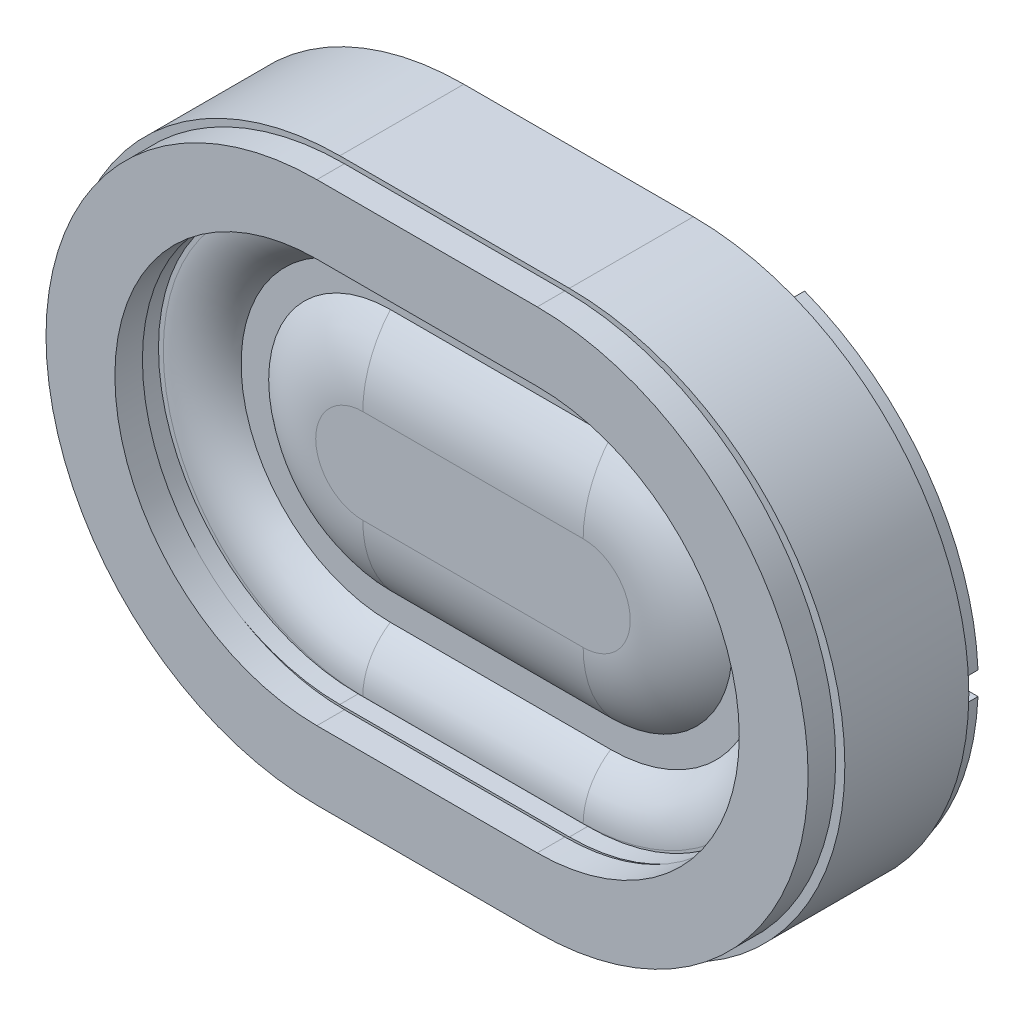
SolidWorks part; units mm, degrees
ref_plane "Front" through (0, 0, 0) normal (0, 0, 1) x (1, 0, 0)
ref_plane "Top" through (0, 0, 0) normal (0, 1, 0) x (1, 0, 0)
ref_plane "Right" through (0, 0, 0) normal (1, 0, 0) x (0, 0, -1)
sketch "Эскиз1" plane through (0, 0, 0) normal (0, 0, 1) x (1, 0, 0)
  line L0 (-2.4, 0) -> (2.4, 0) construction
  line L1 (-2.4, 4.3) -> (2.4, 4.3)
  line L2 (-2.4, -4.3) -> (2.4, -4.3)
  arc A0 (-2.4, 4.3) -> (-2.4, -4.3) centre (-2.4, 0) ccw
  arc A1 (2.4, -4.3) -> (2.4, 4.3) centre (2.4, 0) ccw
  point P2 (0, 0)
  point P8 (6.7, 0)
  point P9 (-6.7, 0)
  dimension "D1" = 8.6
  dimension "D2" = 13.4
extrude "Бобышка-Вытянуть1" add sketch "Эскиз1" along normal blind 1
sketch "Эскиз2" plane through (0, 0, 1) normal (0, 0, 1) x (1, 0, 0)
  line L0 (-2.5, 0) -> (2.5, 0) construction
  line L1 (-2.5, 6) -> (2.5, 6)
  line L2 (-2.5, -6) -> (2.5, -6)
  arc A0 (-2.5, 6) -> (-2.5, -6) centre (-2.5, 0) ccw
  arc A1 (2.5, -6) -> (2.5, 6) centre (2.5, 0) ccw
  point P2 (0, 0)
  point P8 (-8.5, 0)
  point P9 (8.5, 0)
  dimension "D1" = 17
  dimension "D2" = 12
extrude "Бобышка-Вытянуть2" add sketch "Эскиз2" along normal offset from surface (2.7 mm away) 3.7 up to face at (0, 0, 0)
sketch "Эскиз3" plane through (0, 0, 3.7) normal (0, 0, 1) x (1, 0, 0)
  line L0 (-2.4, 0) -> (2.4, 0) construction
  line L1 (-2.4, 5.9) -> (2.4, 5.9)
  line L2 (-2.4, -5.9) -> (2.4, -5.9)
  line L6 (-2.5, -6) -> (2.5, -6) construction
  arc A0 (-2.4, 5.9) -> (-2.4, -5.9) centre (-2.4, 0) ccw
  arc A1 (2.4, -5.9) -> (2.4, 5.9) centre (2.4, 0) ccw
  arc A4 (2.5, -6) -> (2.5, 6) centre (2.5, 0) ccw construction
  point P2 (0, 0)
  dimension "D2" = 0.1
  dimension "D1" = 0.1
extrude "Вытянуть-Тонкостенный1" add sketch "Эскиз3" along normal offset from surface (0.6 mm away) 4.3 separate body thin up to face at (0, 0, 0) thin type one direction reverse wall 1.5
sketch "Эскиз4" plane through (0, 0, 3.7) normal (0, 0, 1) x (1, 0, 0)
  line L0 (-2.4, 0) -> (2.4, 0) construction
  line L1 (-2.4, 3.25) -> (2.4, 3.25)
  line L2 (-2.4, -3.25) -> (2.4, -3.25)
  line L3 (-6.8, 0) -> (-5.65, 0) construction
  line L4 (0, -3.25) -> (0, -4.4) construction
  line L5 (-2.4, -4.4) -> (2.4, -4.4) construction
  line L6 (2.4, 0) -> (-2.4, 0) construction
  line L7 (2.4, -2.65) -> (-2.4, -2.65)
  line L8 (2.4, 2.65) -> (-2.4, 2.65)
  line L9 (0, -2.65) -> (0, -3.25) construction
  line L10 (-5.05, 0) -> (-5.65, 0) construction
  arc A0 (-2.4, 3.25) -> (-2.4, -3.25) centre (-2.4, 0) ccw
  arc A1 (2.4, -3.25) -> (2.4, 3.25) centre (2.4, 0) ccw
  arc A2 (-2.4, 4.4) -> (-2.4, -4.4) centre (-2.4, 0) ccw construction
  arc A3 (2.4, -2.65) -> (2.4, 2.65) centre (2.4, 0) ccw
  arc A4 (-2.4, 2.65) -> (-2.4, -2.65) centre (-2.4, 0) ccw
  point P2 (0, 0)
  point P19 (0, 0)
  dimension "D1" = 6.5
  dimension "D2" = 0.6
extrude "Вырез-Вытянуть1" cut sketch "Эскиз4" against normal offset from surface (1 mm away) 1.6 up to face at (0, 0, 4.3)
sketch "Эскиз5" plane through (0, 0, 3.7) normal (0, 0, 1) x (1, 0, 0)
  line L0 (2.5, 0) -> (-2.5, 0) construction
  line L1 (2.5, -4.35) -> (-2.5, -4.35)
  line L2 (2.5, 4.35) -> (-2.5, 4.35)
  line L3 (0, -4.35) -> (0, -6) construction
  line L4 (-2.5, -6) -> (2.5, -6) construction
  line L5 (-6.85, 0) -> (-8.5, 0) construction
  arc A0 (2.5, -4.35) -> (2.5, 4.35) centre (2.5, 0) ccw
  arc A1 (-2.5, 4.35) -> (-2.5, -4.35) centre (-2.5, 0) ccw
  arc A2 (-2.5, 6) -> (-2.5, -6) centre (-2.5, 0) ccw construction
  point P2 (0, 0)
  dimension "D1" = 8.7
extrude "Вырез-Вытянуть2" cut sketch "Эскиз5" against normal offset from surface (0.4 mm away) 1 up to face at (0, 0, 4.3)
fillet "Скругление1" radius 1.3 4 edges at (5.65, 0, 3.3) (0, 3.25, 3.3) (-5.65, 0, 3.3) (0, -3.25, 3.3)
fillet "Скругление2" radius 2.5 4 edges at (5.05, 0, 3.3) (0, 2.65, 3.3) (-5.05, 0, 3.3) (0, -2.65, 3.3)
sketch "Эскиз6" plane through (0, 0, 1) normal (0, 0, 1) x (1, 0, 0)
  line L0 (6.6927, 0.25) -> (8.4, 0.25)
  line L1 (4.6237, 5.5103) -> (3.4902, 4.1595)
  line L2 (6.6927, -0.25) -> (8.4, -0.25)
  line L3 (4.6237, -5.5103) -> (3.4902, -4.1595)
  line L4 (6.6927, -0.25) -> (6.6927, 0.25) construction
  line L5 (0, 0) -> (6.6927, 0) construction
  line L6 (3.4902, 4.1595) -> (0, 0) construction
  line L7 (4.6237, 5.5103) -> (4.6879, 5.5869) construction
  arc A0 (2.4, -4.3) -> (2.4, 4.3) centre (2.4, 0) ccw construction
  arc A5 (8.4, 0.25) -> (4.6237, 5.5103) centre (2.5, 0) ccw
  arc A6 (8.4, -0.25) -> (4.6237, -5.5103) centre (2.5, 0) cw
  arc A8 (3.4902, 4.1595) -> (6.6927, 0.25) centre (2.4, 0) cw
  arc A9 (6.6927, -0.25) -> (3.4902, -4.1595) centre (2.4, 0) cw
  arc A13 (2.5, -6) -> (2.5, 6) centre (2.5, 0) ccw construction
  point P2 (0, 0)
  point P19 (0, 0)
  dimension "D1" = 0.5
  dimension "D4" = 0.1
  dimension "D2" = 50
extrude "Бобышка-Вытянуть3" add sketch "Эскиз6" against normal blind 0.3
